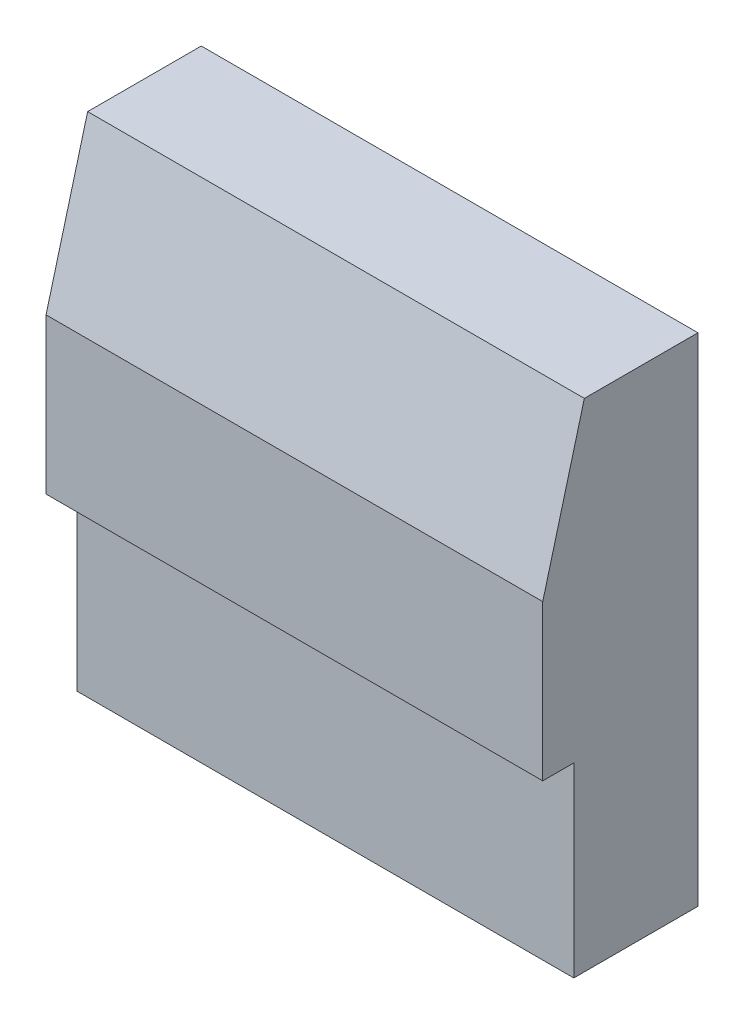
SolidWorks part; units mm, degrees
ref_plane "Alzado" through (0, 0, 0) normal (0, 0, 1) x (1, 0, 0)
ref_plane "Planta" through (0, 0, 0) normal (0, 1, 0) x (1, 0, 0)
ref_plane "Vista lateral" through (0, 0, 0) normal (1, 0, 0) x (0, 0, -1)
sketch "Croquis1" plane through (0, 0, 0) normal (1, 0, 0) x (0, 0, -1)
  line L0 (0, 0) -> (0, 32)
  line L1 (0, 32) -> (-7.3205, 32)
  line L2 (-7.3205, 32) -> (-10, 22)
  line L3 (-10, 22) -> (-10, 12)
  line L4 (-10, 12) -> (-8, 12)
  line L5 (-8, 12) -> (-8, 0)
  line L6 (-8, 0) -> (0, 0)
  dimension "D1" = 2
  dimension "D2" = 12
  dimension "D3" = 32
  dimension "D4" = 10
  dimension "D5" = 15
  dimension "D6" = 8
extrude "Saliente-Extruir1" add sketch "Croquis1" along normal blind 16 and the other way blind 16
